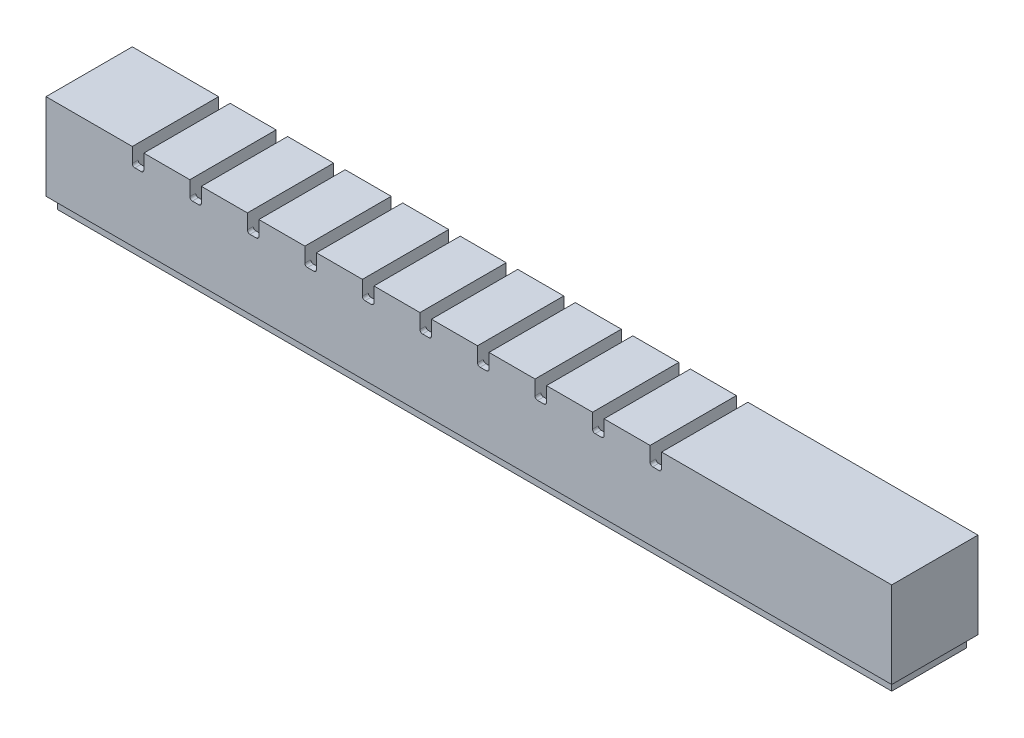
SolidWorks part; units mm, degrees
ref_plane "Front Plane" through (0, 0, 0) normal (0, 0, 1) x (1, 0, 0)
ref_plane "Top Plane" through (0, 0, 0) normal (0, 1, 0) x (1, 0, 0)
ref_plane "Right Plane" through (0, 0, 0) normal (1, 0, 0) x (0, 0, -1)
sketch "Sketch1" plane through (0, 0, 0) normal (0, 0, 1) x (1, 0, 0)
  line L1 (0, 0) -> (8, 0)
  line L2 (0, 0) -> (0, 15)
  line L3 (0, 15) -> (8, 15)
  line L4 (8, 0) -> (8, 15)
  dimension "D1" = 8
  dimension "D2" = 15
extrude "first chamber block" add sketch "Sketch1" along normal blind 15
sketch "Sketch2" plane through (0, 0, 0) normal (0, -1, 0) x (1, 0, 0)
  line L0 (8, 15) -> (8, 0) construction
  line L1 (1, 13) -> (7, 13)
  line L2 (1, 13) -> (1, 2)
  line L3 (1, 2) -> (7, 2)
  line L4 (7, 13) -> (7, 2)
  line L5 (0, 15) -> (0, 0) construction
  line L6 (0, 15) -> (8, 15) construction
  line L7 (0, 0) -> (8, 0) construction
  dimension "D1" = 1
  dimension "D2" = 1
  dimension "D3" = 2
  dimension "D4" = 2
extrude "first chamber cavity" cut sketch "Sketch2" against normal blind 13
sketch "Sketch3" plane through (8, 0, 0) normal (1, 0, 0) x (0, 0, -1)
  line L0 (-15, 0) -> (-15, 15) construction
  line L1 (0, 0) -> (-15, 0)
  line L2 (0, 0) -> (0, 3)
  line L3 (0, 3) -> (-15, 3)
  line L4 (-15, 0) -> (-15, 3)
  dimension "D1" = 3
extrude "chamber spacer" add sketch "Sketch3" along normal blind 2
pattern_linear "pattern chambers" count 11 spacing 10 along (1, 0, 0) of "chamber spacer", "first chamber cavity", "first chamber block"
combine bodies "combine into 1 solid body" operation type add bodies to combine 123 122 121 120 119 118 117 116 115 114 103
sketch "Sketch4" plane through (108, 0, 0) normal (1, 0, 0) x (0, 0, -1)
  line L1 (0, 15) -> (-15, 15)
  line L2 (0, 15) -> (0, 3)
  line L3 (0, 3) -> (-15, 3)
  line L4 (-15, 15) -> (-15, 3)
extrude "thicken end 1" add sketch "Sketch4" along normal up to surface (2 mm away) up to face at (110, 1.5, 7.5)
sketch "Sketch5" plane through (0, 0, 0) normal (-1, 0, 0) x (0, 0, 1)
  line L1 (15, 15) -> (0, 15)
  line L2 (15, 15) -> (15, 0)
  line L3 (15, 0) -> (0, 0)
  line L4 (0, 15) -> (0, 0)
extrude "thicken end 2" add sketch "Sketch5" along normal blind 2
ref_point "center of bottom face"
sketch "Sketch6" plane through (0, 0, 0) normal (0, -1, 0) x (1, 0, 0)
  line L0 (7, 2) -> (7, 13) construction
  line L1 (101, 6.5) -> (7, 6.5)
  line L2 (101, 6.5) -> (101, 8.5)
  line L3 (101, 8.5) -> (7, 8.5)
  line L4 (7, 6.5) -> (7, 8.5)
  line L5 (101, 6.5) -> (7, 8.5) construction
  line L6 (101, 8.5) -> (7, 6.5) construction
  point P0 (54, 7.5)
  dimension "D1" = 2
extrude "central air channel" cut sketch "Sketch6" against normal blind 2
sketch "Skizze3" plane through (8, 0, 0) normal (1, 0, 0) x (0, 0, -1)
  line L0 (-15, 3) -> (-13.5, 3)
  line L1 (0, 3) -> (-15, 3) construction
  line L2 (-13.5, 3) -> (-14, 12.5)
  line L3 (-14, 12.5) -> (-15, 12.5)
  line L4 (-15, 3) -> (-15, 15) construction
  line L5 (-15, 12.5) -> (-15, 3)
  line L6 (-7.5, 15) -> (-7.5, -49985) construction
  line L7 (-15, 15) -> (0, 15) construction
  line L8 (0, 12.5) -> (0, 3)
  line L9 (-1, 12.5) -> (0, 12.5)
  line L10 (-1.5, 3) -> (-1, 12.5)
  line L11 (0, 3) -> (-1.5, 3)
  point P13 (-7.5, 15)
  dimension "D1" = 2.5
  dimension "D2" = 1.5
  dimension "D3" = 1
extrude "Aufsatz-Linear austragen3" add sketch "Skizze3" along normal up to next
sketch "Skizze5" plane through (0, 0, 0) normal (0, 0, -1) x (-1, 0, 0)
  line L0 (-10, 12.5) -> (-10, 3) construction
  line L1 (-10, 12.5) -> (-8, 12.5) construction
  line L2 (-8, 12.5) -> (-8, 3) construction
  line L3 (-10, 12.5) -> (-10, 3) construction
  line L4 (-10, 12.5) -> (-8, 12.5) construction
  line L5 (-8, 12.5) -> (-8, 3) construction
  line L7 (-10, 12.5) -> (-8, 12.5)
  line L8 (-10, 12.5) -> (-10, 12.45)
  line L9 (-9.55, 12) -> (-8.45, 12)
  line L10 (-8, 12.5) -> (-8, 12.45)
  arc A0 (-8.45, 12) -> (-8, 12.45) centre (-8.45, 12.45) ccw
  arc A1 (-10, 12.45) -> (-9.55, 12) centre (-9.55, 12.45) ccw
  point P9 (-8, 12)
  dimension "D1" = 0.45
  dimension "D2" = 0.5
extrude "Schnitt-Linear austragen2" cut sketch "Skizze5" against normal through all
pattern_linear "Lineares Muster8" count 10 spacing 10 along (1, 0, 0) of "Aufsatz-Linear austragen3", "Schnitt-Linear austragen2"
sketch "Sketch17" plane through (110, 0, 0) normal (1, 0, 0) x (0, 0, -1)
  line L4 (0, 0) -> (0, 15)
  line L5 (0, 15) -> (-15, 15)
  line L6 (-15, 15) -> (-15, 0)
  line L7 (-15, 0) -> (0, 0)
  line L8 (0, 0) -> (0, 15)
  line L9 (0, 15) -> (-15, 15)
  line L10 (-15, 15) -> (-15, 0)
  line L11 (-15, 0) -> (0, 0)
  dimension "D1" = 0
extrude "Boss-Extrude1" add sketch "Sketch17" along normal blind 30
sketch "Sketch18" plane through (-2, 0, 0) normal (-1, 0, 0) x (0, 0, 1)
  line L4 (15, 0) -> (15, 15)
  line L5 (15, 15) -> (0, 15)
  line L6 (0, 15) -> (0, 0)
  line L7 (0, 0) -> (15, 0)
  line L8 (15, 0) -> (15, 15)
  line L9 (15, 15) -> (0, 15)
  line L10 (0, 15) -> (0, 0)
  line L11 (0, 0) -> (15, 0)
  dimension "D1" = 0
extrude "Boss-Extrude2" add sketch "Sketch18" along normal blind 5
sketch "Sketch19" plane through (0, 0, 0) normal (0, -1, 0) x (1, 0, 0)
  line L0 (-7, 15) -> (140, 15) construction
  line L1 (140, 0) -> (107, 0) construction
  line L2 (140, 0) -> (140, 15) construction
  line L3 (140, 15) -> (107, 15) construction
  line L4 (107, 0) -> (107, 15) construction
  line L5 (138, 2) -> (109, 2)
  line L6 (109, 2) -> (109, 13)
  line L7 (138, 13) -> (109, 13)
  line L8 (138, 2) -> (138, 13)
  line L9 (107, 2) -> (107, 13) construction
  line L10 (131.8284, 7.5) -> (137.3284, 2)
  line L11 (134.5, 2) -> (130.4142, 6.0858)
  line L12 (123.5, 13) -> (118, 7.5)
  line L13 (131.8284, 7.5) -> (137.3284, 13)
  line L15 (120.6716, 13) -> (116.5858, 8.9142)
  line L16 (123.5, 15.8284) -> (111.0858, 3.4142) construction
  line L17 (136.668, 8.5647) -> (134.2315, 5.0969) construction
  line L18 (138, 2) -> (137.3284, 2) construction
  line L19 (134.5, 13) -> (130.4142, 8.9142)
  line L20 (123.5, 2) -> (118, 7.5)
  line L21 (137.3284, 2) -> (137.3284, -1.3796) construction
  line L23 (120.6716, 2) -> (116.5858, 6.0858)
  line L25 (138.3045, 7.4149) -> (134.5, 2) construction
  line L27 (130.4142, 6.0858) -> (126.3284, 2)
  line L28 (129, 7.5) -> (123.5, 13)
  line L29 (130.4142, 8.9142) -> (126.3284, 13)
  line L30 (134.5, 2) -> (123.5, 13) construction
  line L31 (129, 7.5) -> (123.5, 2)
  line L32 (134.2315, 5.0969) -> (123.5, 15.8284) construction
  line L33 (115.1716, 7.5) -> (109.6716, 2)
  line L34 (116.5858, 8.9142) -> (112.5, 13)
  line L35 (115.1716, 7.5) -> (109.6716, 13)
  line L36 (116.5858, 6.0858) -> (112.5, 2)
  line L37 (124.5, 3) -> (122.5, 3) construction
  line L38 (123.5, 13) -> (112.5, 2) construction
  line L39 (124.5, 3) -> (124.5, 12)
  line L40 (124.5, 12) -> (122.5, 12) construction
  line L41 (122.5, 3) -> (122.5, 12)
  line L42 (109.6716, 2) -> (109.6716, -1.3796) construction
  line L43 (109, 2) -> (109, -1.3796) construction
  line L44 (138, -1.3796) -> (137.3284, -1.3796) construction
  line L45 (138, -1.3796) -> (138, 2) construction
  line L46 (137.3284, -1.3796) -> (109.6716, -1.3796) construction
  line L47 (109.6716, -1.3796) -> (109, -1.3796) construction
  line L48 (109.6716, 2) -> (109.6716, 13)
  line L49 (137.3284, 2) -> (137.3284, 13)
  dimension "D2" = 2
  dimension "D4" = 2
  dimension "D5" = 2
  dimension "D6" = 45
  dimension "D8" = 2
  dimension "D1" = 2
  dimension "D3" = 2
extrude "Cut-Extrude1" cut sketch "Sketch19" against normal offset from surface (12 mm away) 3 contours L13 L10 L5 L8 L7 | L11 L27 L5 | L29 L19 L7 | L23 L36 L5 | L34 L15 L7 | L33 L35 L6 | L39 L31 L28 | L20 L41 L12
sketch "Sketch20" plane through (0, 0, 0) normal (0, -1, 0) x (1, 0, 0)
  line L0 (109.1716, 3.5) -> (109.1716, 5.5)
  line L1 (107.5, 11.5) -> (109.1716, 11.5)
  line L2 (107.5, 11.5) -> (107.5, 9.5)
  line L3 (107.5, 9.5) -> (109.1716, 9.5)
  line L4 (-5, 13) -> (-5, 2)
  line L5 (-5, 2) -> (138, 2)
  line L6 (138, 2) -> (138, 13)
  line L7 (138, 13) -> (-5, 13)
  line L8 (139, 1) -> (139, 14)
  line L9 (-6, 1) -> (139, 1)
  line L10 (139, 14) -> (-6, 14)
  line L11 (-6, 14) -> (-6, 1)
  line L12 (139, 1) -> (139, 14)
  line L13 (-6, 1) -> (139, 1)
  line L14 (139, 14) -> (-6, 14)
  line L15 (-6, 14) -> (-6, 1)
  line L16 (109.1716, 11.5) -> (109.1716, 9.5)
  line L17 (107.5, 5.5) -> (109.1716, 5.5)
  line L18 (107.5, 3.5) -> (107.5, 5.5)
  line L19 (8, 11.5) -> (10, 11.5)
  line L20 (1, 7.5) -> (50001, 7.5) construction
  line L21 (1, 13) -> (1, 2) construction
  line L22 (10, 13) -> (10, 9.5)
  line L23 (10, 9.5) -> (8, 9.5)
  line L24 (8, 9.5) -> (8, 13)
  line L25 (10, 11.5) -> (10, 9.5)
  line L26 (10, 9.5) -> (8, 9.5)
  line L27 (8, 9.5) -> (8, 11.5)
  line L28 (10, 5.5) -> (8, 5.5)
  line L29 (10, 3.5) -> (10, 5.5)
  line L30 (8, 3.5) -> (10, 3.5)
  line L31 (138, 13) -> (138, 2)
  line L32 (-5, 13) -> (138, 13)
  line L33 (-5, 2) -> (-5, 13)
  line L34 (8, 5.5) -> (8, 3.5)
  line L35 (18, 9.5) -> (18, 11.5)
  line L36 (18, 11.5) -> (20, 11.5)
  line L37 (20, 11.5) -> (20, 9.5)
  line L38 (20, 9.5) -> (18, 9.5)
  line L39 (20, 5.5) -> (18, 5.5)
  line L40 (18, 5.5) -> (18, 3.5)
  line L41 (18, 3.5) -> (20, 3.5)
  line L42 (20, 3.5) -> (20, 5.5)
  line L43 (148, 13) -> (5, 13)
  line L44 (28, 9.5) -> (28, 11.5)
  line L45 (28, 11.5) -> (30, 11.5)
  line L46 (30, 11.5) -> (30, 9.5)
  line L47 (30, 9.5) -> (28, 9.5)
  line L48 (30, 5.5) -> (28, 5.5)
  line L49 (28, 5.5) -> (28, 3.5)
  line L50 (28, 3.5) -> (30, 3.5)
  line L51 (30, 3.5) -> (30, 5.5)
  line L52 (158, 13) -> (15, 13)
  line L53 (38, 9.5) -> (38, 11.5)
  line L54 (38, 11.5) -> (40, 11.5)
  line L55 (40, 11.5) -> (40, 9.5)
  line L56 (40, 9.5) -> (38, 9.5)
  line L57 (40, 5.5) -> (38, 5.5)
  line L58 (38, 5.5) -> (38, 3.5)
  line L59 (38, 3.5) -> (40, 3.5)
  line L60 (40, 3.5) -> (40, 5.5)
  line L61 (168, 13) -> (25, 13)
  line L62 (48, 9.5) -> (48, 11.5)
  line L63 (48, 11.5) -> (50, 11.5)
  line L64 (50, 11.5) -> (50, 9.5)
  line L65 (50, 9.5) -> (48, 9.5)
  line L66 (50, 5.5) -> (48, 5.5)
  line L67 (48, 5.5) -> (48, 3.5)
  line L68 (48, 3.5) -> (50, 3.5)
  line L69 (50, 3.5) -> (50, 5.5)
  line L70 (178, 13) -> (35, 13)
  line L71 (58, 9.5) -> (58, 11.5)
  line L72 (58, 11.5) -> (60, 11.5)
  line L73 (60, 11.5) -> (60, 9.5)
  line L74 (60, 9.5) -> (58, 9.5)
  line L75 (60, 5.5) -> (58, 5.5)
  line L76 (58, 5.5) -> (58, 3.5)
  line L77 (58, 3.5) -> (60, 3.5)
  line L78 (60, 3.5) -> (60, 5.5)
  line L79 (188, 13) -> (45, 13)
  line L80 (68, 9.5) -> (68, 11.5)
  line L81 (68, 11.5) -> (70, 11.5)
  line L82 (70, 11.5) -> (70, 9.5)
  line L83 (70, 9.5) -> (68, 9.5)
  line L84 (70, 5.5) -> (68, 5.5)
  line L85 (68, 5.5) -> (68, 3.5)
  line L86 (68, 3.5) -> (70, 3.5)
  line L87 (70, 3.5) -> (70, 5.5)
  line L88 (198, 13) -> (55, 13)
  line L89 (78, 9.5) -> (78, 11.5)
  line L90 (78, 11.5) -> (80, 11.5)
  line L91 (80, 11.5) -> (80, 9.5)
  line L92 (80, 9.5) -> (78, 9.5)
  line L93 (80, 5.5) -> (78, 5.5)
  line L94 (78, 5.5) -> (78, 3.5)
  line L95 (78, 3.5) -> (80, 3.5)
  line L96 (80, 3.5) -> (80, 5.5)
  line L97 (208, 13) -> (65, 13)
  line L98 (88, 9.5) -> (88, 11.5)
  line L99 (88, 11.5) -> (90, 11.5)
  line L100 (90, 11.5) -> (90, 9.5)
  line L101 (90, 9.5) -> (88, 9.5)
  line L102 (90, 5.5) -> (88, 5.5)
  line L103 (88, 5.5) -> (88, 3.5)
  line L104 (88, 3.5) -> (90, 3.5)
  line L105 (90, 3.5) -> (90, 5.5)
  line L106 (218, 13) -> (75, 13)
  line L107 (98, 9.5) -> (98, 11.5)
  line L108 (98, 11.5) -> (100, 11.5)
  line L109 (100, 11.5) -> (100, 9.5)
  line L110 (100, 9.5) -> (98, 9.5)
  line L111 (100, 5.5) -> (98, 5.5)
  line L112 (98, 5.5) -> (98, 3.5)
  line L113 (98, 3.5) -> (100, 3.5)
  line L114 (100, 3.5) -> (100, 5.5)
  line L115 (228, 13) -> (85, 13)
  line L116 (8, 9.5) -> (8, 11.5)
  line L117 (8, 11.5) -> (10, 11.5)
  line L118 (10, 11.5) -> (10, 9.5)
  line L119 (10, 9.5) -> (8, 9.5)
  line L120 (10, 5.5) -> (8, 5.5)
  line L121 (8, 5.5) -> (8, 3.5)
  line L122 (8, 3.5) -> (10, 3.5)
  line L123 (10, 3.5) -> (10, 5.5)
  line L124 (138, 13) -> (-5, 13)
  line L125 (18, 9.5) -> (18, 11.5)
  line L126 (18, 11.5) -> (20, 11.5)
  line L127 (20, 11.5) -> (20, 9.5)
  line L128 (20, 9.5) -> (18, 9.5)
  line L129 (20, 5.5) -> (18, 5.5)
  line L130 (18, 5.5) -> (18, 3.5)
  line L131 (18, 3.5) -> (20, 3.5)
  line L132 (20, 3.5) -> (20, 5.5)
  line L133 (148, 13) -> (5, 13)
  line L134 (28, 9.5) -> (28, 11.5)
  line L135 (28, 11.5) -> (30, 11.5)
  line L136 (30, 11.5) -> (30, 9.5)
  line L137 (30, 9.5) -> (28, 9.5)
  line L138 (30, 5.5) -> (28, 5.5)
  line L139 (28, 5.5) -> (28, 3.5)
  line L140 (28, 3.5) -> (30, 3.5)
  line L141 (30, 3.5) -> (30, 5.5)
  line L142 (158, 13) -> (15, 13)
  line L143 (38, 9.5) -> (38, 11.5)
  line L144 (38, 11.5) -> (40, 11.5)
  line L145 (40, 11.5) -> (40, 9.5)
  line L146 (40, 9.5) -> (38, 9.5)
  line L147 (40, 5.5) -> (38, 5.5)
  line L148 (38, 5.5) -> (38, 3.5)
  line L149 (38, 3.5) -> (40, 3.5)
  line L150 (40, 3.5) -> (40, 5.5)
  line L151 (168, 13) -> (25, 13)
  line L152 (48, 9.5) -> (48, 11.5)
  line L153 (48, 11.5) -> (50, 11.5)
  line L154 (50, 11.5) -> (50, 9.5)
  line L155 (50, 9.5) -> (48, 9.5)
  line L156 (50, 5.5) -> (48, 5.5)
  line L157 (48, 5.5) -> (48, 3.5)
  line L158 (48, 3.5) -> (50, 3.5)
  line L159 (50, 3.5) -> (50, 5.5)
  line L160 (178, 13) -> (35, 13)
  line L161 (58, 9.5) -> (58, 11.5)
  line L162 (58, 11.5) -> (60, 11.5)
  line L163 (60, 11.5) -> (60, 9.5)
  line L164 (60, 9.5) -> (58, 9.5)
  line L165 (60, 5.5) -> (58, 5.5)
  line L166 (58, 5.5) -> (58, 3.5)
  line L167 (58, 3.5) -> (60, 3.5)
  line L168 (60, 3.5) -> (60, 5.5)
  line L169 (188, 13) -> (45, 13)
  line L170 (68, 9.5) -> (68, 11.5)
  line L171 (68, 11.5) -> (70, 11.5)
  line L172 (70, 11.5) -> (70, 9.5)
  line L173 (70, 9.5) -> (68, 9.5)
  line L174 (70, 5.5) -> (68, 5.5)
  line L175 (68, 5.5) -> (68, 3.5)
  line L176 (68, 3.5) -> (70, 3.5)
  line L177 (70, 3.5) -> (70, 5.5)
  line L178 (198, 13) -> (55, 13)
  line L179 (78, 9.5) -> (78, 11.5)
  line L180 (78, 11.5) -> (80, 11.5)
  line L181 (80, 11.5) -> (80, 9.5)
  line L182 (80, 9.5) -> (78, 9.5)
  line L183 (80, 5.5) -> (78, 5.5)
  line L184 (78, 5.5) -> (78, 3.5)
  line L185 (78, 3.5) -> (80, 3.5)
  line L186 (80, 3.5) -> (80, 5.5)
  line L187 (208, 13) -> (65, 13)
  line L188 (88, 9.5) -> (88, 11.5)
  line L189 (88, 11.5) -> (90, 11.5)
  line L190 (90, 11.5) -> (90, 9.5)
  line L191 (90, 9.5) -> (88, 9.5)
  line L192 (90, 5.5) -> (88, 5.5)
  line L193 (88, 5.5) -> (88, 3.5)
  line L194 (88, 3.5) -> (90, 3.5)
  line L195 (90, 3.5) -> (90, 5.5)
  line L196 (218, 13) -> (75, 13)
  line L197 (-2, 9.5) -> (-2, 11.5)
  line L198 (-2, 11.5) -> (0, 11.5)
  line L199 (0, 11.5) -> (0, 9.5)
  line L200 (0, 9.5) -> (-2, 9.5)
  line L201 (0, 5.5) -> (-2, 5.5)
  line L202 (-2, 5.5) -> (-2, 3.5)
  line L203 (-2, 3.5) -> (0, 3.5)
  line L204 (0, 3.5) -> (0, 5.5)
  line L205 (128, 13) -> (-15, 13)
  line L206 (107.5, 3.5) -> (109.1716, 3.5)
  line L207 (107, 12.4846) -> (109.6716, 12.4846) construction
  line L208 (107, 2) -> (107, 13) construction
  line L209 (109.6716, 2) -> (109.6716, 13) construction
  line L210 (108.3358, 12.4846) -> (108.3358, -49987.5154) construction
  circle A0 centre (116.5858, 7.5) radius 1
  circle A1 centre (130.4142, 7.5) radius 1
  point P18 (1, 7.5)
  point P195 (108.3358, 12.4846)
  dimension "D10" = 2
  dimension "D4" = 2
  dimension "D7" = 8
  dimension "D8" = 8
  dimension "D9" = 0.5
  dimension "D1" = 1
  dimension "D2" = 1
  dimension "D3" = 1
  dimension "D5" = 10
  dimension "D6" = 2
extrude "nipple_extrude" add sketch "Sketch20" along normal blind 2 contours L205 L32 L43 L52 L61 L70 L79 L88 L97 L106 L196 L7 L12 L14 L15 | L4 L205 L15 L13 L12 L43 L6 L5 | L200 L199 L198 L197 | L203 L204 L201 L202 | L27 L26 L25 L19 | L28 L34 L30 L29 | L38 L37 L36 L35 | L41 L42 L39 L40 | L50 L51 L48 L49 | L47 L46 L45 L44 | L56 L55 L54 L53 | L59 L60 L57 L58 | L65 L64 L63 L62 | L68 L69 L66 L67 | L77 L78 L75 L76 | L74 L73 L72 L71 | L83 L82 L81 L80 | L86 L87 L84 L85 | L92 L91 L90 L89 | L95 L96 L93 L94 | L101 L100 L99 L98 | L104 L105 L102 L103 | L110 L109 L108 L107 | L113 L114 L111 L112 | L18 L206 L0 L17 | L16 L1 L2 L3 | A0 | A1
